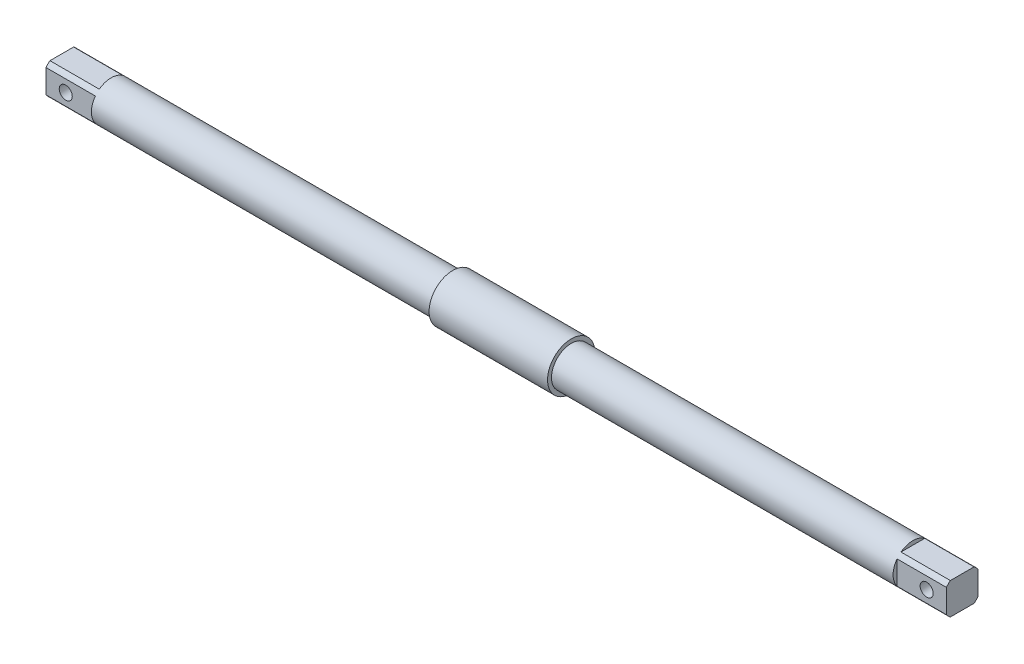
SolidWorks part; units mm, degrees
material "304"
ref_plane "前视基准面" through (0, 0, 0) normal (0, 0, 1) x (1, 0, 0)
ref_plane "上视基准面" through (0, 0, 0) normal (0, 1, 0) x (1, 0, 0)
ref_plane "右视基准面" through (0, 0, 0) normal (1, 0, 0) x (0, 0, -1)
sketch "草图1" plane through (0, 0, 0) normal (0, 0, 1) x (1, 0, 0)
  line L0 (-177.8106, 0) -> (177.8106, 0) construction
  line L1 (114, 0) -> (114, 5)
  line L2 (-114, 5) -> (-114, 0)
  line L5 (-15, 5) -> (-15, 6)
  line L6 (-15, 6) -> (15, 6)
  line L7 (15, 6) -> (15, 5)
  line L10 (15, 5) -> (114, 5)
  line L14 (0, 0) -> (0, 12) construction
  line L15 (-114, 0) -> (114, 0)
  line L16 (-15, 5) -> (-114, 5)
  point P19 (0, 6)
  dimension "D2" = 99
  dimension "D3" = 10
  dimension "D5" = 30
  dimension "D6" = 99
  dimension "D7" = 10
  dimension "D12" = 12
revolve "旋转1" add sketch "草图1" angle 360 about L15
sketch "草图2" plane through (114, 0, 0) normal (1, 0, 0) x (0, 0, -1)
  line L1 (-4, 4) -> (4, 4)
  line L2 (-4, 4) -> (-4, -4)
  line L3 (-4, -4) -> (4, -4)
  line L4 (4, 4) -> (4, -4)
  line L5 (-4, 4) -> (4, -4) construction
  line L6 (-4, -4) -> (4, 4) construction
  point P0 (0, 0)
  dimension "D1" = 8
  dimension "D2" = 8
extrude "切除-拉伸1" cut sketch "草图2" against normal blind 12.5 flip side to cut
mirror "镜向2" about plane through (0, 0, 0) normal (1, 0, 0) of "切除-拉伸1"
hole_wizard "M4 螺纹孔1" positions "草图4" profile "草图3" tap size "M4" standard "GB" end condition through all
sketch "草图4" plane through (0, 0, 4) normal (0, 0, 1) x (1, 0, 0)
  line L0 (114, 3) -> (114, -3) construction
  line L1 (-114, -3) -> (-114, 3) construction
  point P0 (109, 0)
  point P5 (-109, 0)
  point P8 (-114, 0)
  dimension "D1" = 5
  dimension "D2" = 5
sketch "草图3" plane through (109, 0, 4) normal (1, 0, 0) x (0, -1, 0)
  line L0 (0, 0) -> (0, 10)
  line L1 (0, 10) -> (1.65, 10)
  line L2 (1.65, 10) -> (1.65, 0)
  line L5 (1.65, 0) -> (0, 0)
  line L11 (0, -6.35) -> (0, 107.95) construction
  dimension "通孔螺纹孔钻头直径" = 3.3
  dimension "通孔螺纹孔钻头深度" = 10
cosmetic thread "孔螺蚊线1" parameters "D2"=4
cosmetic thread "孔螺蚊线2" parameters "D2"=4
